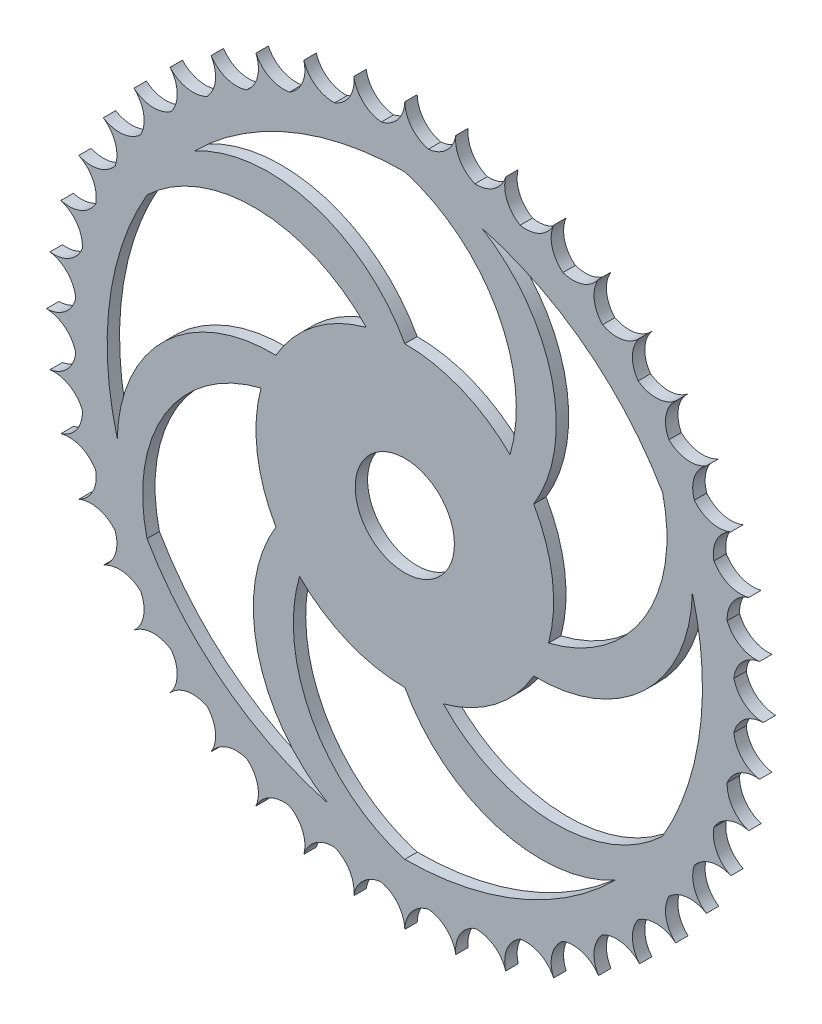
SolidWorks part; units mm, degrees
ref_plane "Alzado" through (0, 0, 0) normal (0, 0, 1) x (1, 0, 0)
ref_plane "Planta" through (0, 0, 0) normal (0, 1, 0) x (1, 0, 0)
ref_plane "Vista lateral" through (0, 0, 0) normal (1, 0, 0) x (0, 0, -1)
sketch "Croquis2" plane through (0, 0, 0) normal (0, 0, 1) x (1, 0, 0)
  line L0 (0, 0) -> (0, 131.9446) construction
  line L1 (0, 0) -> (9.1932, 128.5376) construction
  line L2 (0, 0) -> (-8.8645, 123.9425) construction
  line L3 (-6.025, 84.2398) -> (-6.0245, 84.2341)
  circle A0 centre (0, 0) radius 92.075
  arc A3 (0, 92.075) -> (6.025, 84.2398) centre (7.8948, 91.9118) ccw
  arc A4 (0, 92.075) -> (-6.025, 84.2398) centre (-7.8948, 91.9118) cw
  arc A5 (13.1036, 91.1378) -> (6.025, 84.2398) centre (5.2659, 92.0998) cw
  arc A6 (13.1036, 91.1378) -> (17.9522, 82.5249) centre (20.8949, 89.8527) ccw
  arc A7 (25.9405, 88.3453) -> (17.9522, 82.5249) centre (18.3195, 90.4129) cw
  arc A8 (25.9405, 88.3453) -> (29.514, 79.1301) centre (33.4696, 85.9645) ccw
  arc A9 (38.2493, 83.7544) -> (29.514, 79.1301) centre (31.0001, 86.8855) cw
  arc A10 (38.2493, 83.7544) -> (40.475, 74.1244) centre (45.3629, 80.3262) ccw
  arc A11 (49.7795, 77.4584) -> (40.475, 74.1244) centre (43.0497, 81.5894) cw
  arc A12 (49.7795, 77.4584) -> (50.612, 67.6097) centre (56.3328, 73.0528) ccw
  arc A13 (60.2963, 69.5856) -> (50.612, 67.6097) centre (54.2229, 74.6323) cw
  arc A14 (60.2963, 69.5856) -> (59.7187, 59.7187) centre (66.1559, 64.2923) ccw
  arc A15 (69.5856, 60.2963) -> (59.7187, 59.7187) centre (64.2923, 66.1559) cw
  arc A16 (69.5856, 60.2963) -> (67.6097, 50.612) centre (74.6323, 54.2229) ccw
  arc A17 (77.4584, 49.7795) -> (67.6097, 50.612) centre (73.0528, 56.3328) cw
  arc A18 (77.4584, 49.7795) -> (74.1244, 40.475) centre (81.5894, 43.0497) ccw
  arc A19 (83.7544, 38.2493) -> (74.1244, 40.475) centre (80.3262, 45.3629) cw
  arc A20 (83.7544, 38.2493) -> (79.1301, 29.514) centre (86.8855, 31.0001) ccw
  arc A21 (88.3453, 25.9405) -> (79.1301, 29.514) centre (85.9644, 33.4696) cw
  arc A22 (88.3453, 25.9405) -> (82.5249, 17.9522) centre (90.4129, 18.3195) ccw
  arc A23 (91.1378, 13.1036) -> (82.5249, 17.9522) centre (89.8527, 20.8949) cw
  arc A24 (91.1378, 13.1036) -> (84.2398, 6.025) centre (92.0998, 5.2659) ccw
  arc A25 (92.075, 0) -> (84.2398, 6.025) centre (91.9118, 7.8948) cw
  arc A26 (92.075, 0) -> (84.2398, -6.0249) centre (91.9118, -7.8948) ccw
  arc A27 (91.1378, -13.1036) -> (84.2398, -6.0249) centre (92.0998, -5.2659) cw
  arc A28 (91.1378, -13.1036) -> (82.5249, -17.9522) centre (89.8527, -20.8949) ccw
  arc A29 (88.3453, -25.9405) -> (82.5249, -17.9522) centre (90.4129, -18.3195) cw
  arc A30 (88.3453, -25.9405) -> (79.1301, -29.514) centre (85.9644, -33.4696) ccw
  arc A31 (83.7544, -38.2493) -> (79.1301, -29.514) centre (86.8855, -31.0001) cw
  arc A32 (83.7544, -38.2493) -> (74.1244, -40.475) centre (80.3262, -45.3629) ccw
  arc A33 (77.4584, -49.7795) -> (74.1244, -40.475) centre (81.5894, -43.0497) cw
  arc A34 (77.4584, -49.7795) -> (67.6097, -50.612) centre (73.0528, -56.3328) ccw
  arc A35 (69.5856, -60.2963) -> (67.6097, -50.612) centre (74.6323, -54.2229) cw
  arc A36 (69.5856, -60.2963) -> (59.7187, -59.7187) centre (64.2923, -66.1559) ccw
  arc A37 (60.2963, -69.5856) -> (59.7187, -59.7187) centre (66.1559, -64.2922) cw
  arc A38 (60.2963, -69.5856) -> (50.612, -67.6097) centre (54.2229, -74.6323) ccw
  arc A39 (49.7795, -77.4584) -> (50.612, -67.6097) centre (56.3328, -73.0528) cw
  arc A40 (49.7795, -77.4584) -> (40.475, -74.1244) centre (43.0497, -81.5894) ccw
  arc A41 (38.2493, -83.7544) -> (40.475, -74.1244) centre (45.3629, -80.3262) cw
  arc A42 (38.2493, -83.7544) -> (29.514, -79.1301) centre (31.0001, -86.8855) ccw
  arc A43 (25.9405, -88.3453) -> (29.514, -79.1301) centre (33.4696, -85.9644) cw
  arc A44 (25.9405, -88.3453) -> (17.9522, -82.5249) centre (18.3195, -90.4129) ccw
  arc A45 (13.1036, -91.1378) -> (17.9522, -82.5249) centre (20.8949, -89.8527) cw
  arc A46 (13.1036, -91.1378) -> (6.025, -84.2398) centre (5.2659, -92.0998) ccw
  arc A47 (0, -92.075) -> (6.025, -84.2398) centre (7.8948, -91.9117) cw
  arc A48 (0, -92.075) -> (-6.025, -84.2398) centre (-7.8948, -91.9117) ccw
  arc A49 (-13.1036, -91.1378) -> (-6.025, -84.2398) centre (-5.2659, -92.0998) cw
  arc A50 (-13.1036, -91.1378) -> (-17.9522, -82.5249) centre (-20.8949, -89.8527) ccw
  arc A51 (-25.9405, -88.3453) -> (-17.9522, -82.5249) centre (-18.3195, -90.4129) cw
  arc A52 (-25.9405, -88.3453) -> (-29.514, -79.1301) centre (-33.4696, -85.9644) ccw
  arc A53 (-38.2493, -83.7544) -> (-29.514, -79.1301) centre (-31.0001, -86.8855) cw
  arc A54 (-38.2493, -83.7544) -> (-40.475, -74.1244) centre (-45.3629, -80.3262) ccw
  arc A55 (-49.7795, -77.4584) -> (-40.475, -74.1244) centre (-43.0497, -81.5894) cw
  arc A56 (-49.7795, -77.4584) -> (-50.612, -67.6097) centre (-56.3328, -73.0528) ccw
  arc A57 (-60.2963, -69.5856) -> (-50.612, -67.6097) centre (-54.2229, -74.6323) cw
  arc A58 (-60.2963, -69.5856) -> (-59.7187, -59.7187) centre (-66.1559, -64.2922) ccw
  arc A59 (-69.5856, -60.2963) -> (-59.7187, -59.7187) centre (-64.2923, -66.1559) cw
  arc A60 (-69.5856, -60.2963) -> (-67.6097, -50.612) centre (-74.6323, -54.2229) ccw
  arc A61 (-77.4584, -49.7795) -> (-67.6097, -50.612) centre (-73.0528, -56.3328) cw
  arc A62 (-77.4584, -49.7795) -> (-74.1244, -40.475) centre (-81.5894, -43.0497) ccw
  arc A63 (-83.7544, -38.2493) -> (-74.1244, -40.475) centre (-80.3262, -45.3629) cw
  arc A64 (-83.7544, -38.2493) -> (-79.1301, -29.514) centre (-86.8855, -31.0001) ccw
  arc A65 (-88.3453, -25.9405) -> (-79.1301, -29.514) centre (-85.9644, -33.4696) cw
  arc A66 (-88.3453, -25.9405) -> (-82.5249, -17.9522) centre (-90.4129, -18.3195) ccw
  arc A67 (-91.1378, -13.1036) -> (-82.5249, -17.9522) centre (-89.8527, -20.8949) cw
  arc A68 (-91.1378, -13.1036) -> (-84.2398, -6.0249) centre (-92.0998, -5.2659) ccw
  arc A69 (-92.075, 0) -> (-84.2398, -6.0249) centre (-91.9118, -7.8948) cw
  arc A70 (-92.075, 0) -> (-84.2398, 6.025) centre (-91.9118, 7.8948) ccw
  arc A71 (-91.1378, 13.1036) -> (-84.2398, 6.025) centre (-92.0998, 5.2659) cw
  arc A72 (-91.1378, 13.1036) -> (-82.5249, 17.9522) centre (-89.8527, 20.8949) ccw
  arc A73 (-88.3453, 25.9405) -> (-82.5249, 17.9522) centre (-90.4129, 18.3195) cw
  arc A74 (-88.3453, 25.9405) -> (-79.1301, 29.514) centre (-85.9644, 33.4696) ccw
  arc A75 (-83.7544, 38.2493) -> (-79.1301, 29.514) centre (-86.8855, 31.0001) cw
  arc A76 (-83.7544, 38.2493) -> (-74.1244, 40.475) centre (-80.3262, 45.3629) ccw
  arc A77 (-77.4584, 49.7795) -> (-74.1244, 40.475) centre (-81.5894, 43.0497) cw
  arc A78 (-77.4584, 49.7795) -> (-67.6097, 50.612) centre (-73.0528, 56.3328) ccw
  arc A79 (-69.5856, 60.2963) -> (-67.6097, 50.612) centre (-74.6323, 54.2229) cw
  arc A80 (-69.5856, 60.2963) -> (-59.7187, 59.7187) centre (-64.2923, 66.1559) ccw
  arc A81 (-60.2963, 69.5856) -> (-59.7187, 59.7187) centre (-66.1559, 64.2923) cw
  arc A82 (-60.2963, 69.5856) -> (-50.612, 67.6097) centre (-54.2229, 74.6323) ccw
  arc A83 (-49.7795, 77.4584) -> (-50.612, 67.6097) centre (-56.3328, 73.0528) cw
  arc A84 (-49.7795, 77.4584) -> (-40.475, 74.1244) centre (-43.0497, 81.5894) ccw
  arc A85 (-38.2493, 83.7544) -> (-40.475, 74.1244) centre (-45.3629, 80.3262) cw
  arc A86 (-38.2493, 83.7544) -> (-29.514, 79.1301) centre (-31.0001, 86.8855) ccw
  arc A87 (-25.9405, 88.3453) -> (-29.514, 79.1301) centre (-33.4696, 85.9645) cw
  arc A88 (-25.9405, 88.3453) -> (-17.9522, 82.5249) centre (-18.3195, 90.4129) ccw
  arc A89 (-13.1036, 91.1378) -> (-17.9522, 82.5249) centre (-20.8949, 89.8527) cw
  arc A90 (-13.1036, 91.1378) -> (-6.025, 84.2398) centre (-5.2659, 92.0998) ccw
  point P111 (0, 0)
  point P232 (0, 0)
  dimension "D1" = 184.15
  dimension "D5" = 44
  dimension "D3" = 4.091
  dimension "D4" = 4.091
extrude "Saliente-Extruir1" add sketch "Croquis2" along normal mid plane 3.175 contours A90 A89 A88 A87 A86 A85 A84 A83 A82 A81 A80 A79 A78 A77 A76 A75 A74 A73 A72 A71 A70 A69 A68 A67 A66 A65 A64 A63 A62 A61 A60 A59 A58 A57 A56 A55 A54 A53 A52 A51 A50 A49 A48 A47 A46 A45 A44 A43 A42 A41 A40 region at (0, 0, 0)
sketch "Croquis3" plane through (0, 0, 1.5875) normal (0, 0, 1) x (1, 0, 0)
  line L1 (0, 38.1) -> (0, 91.7485) construction
  arc A0 (0, 76.2) -> (-53.8815, 53.8815) centre (0, 0) ccw
  arc A1 (26.9408, 26.9408) -> (0, 38.1) centre (0, 0) ccw
  arc A2 (-53.8815, 53.8815) -> (0, 38.1) centre (-34.8315, 19.05) cw
  arc A3 (26.9408, 26.9408) -> (0, 76.2) centre (-11.1592, 38.1) ccw
  arc A4 (65.9911, 38.1) -> (19.722, 73.6035) centre (0, 0) ccw
  arc A5 (19.722, 73.6035) -> (32.9956, 19.05) centre (-0.918, 39.69) cw
  arc A6 (36.8018, -9.861) -> (32.9956, 19.05) centre (0, 0) ccw
  arc A7 (36.8018, -9.861) -> (65.9911, 38.1) centre (27.416, 28.7142) ccw
  arc A8 (65.9911, -38.1) -> (73.6035, 19.722) centre (0, 0) ccw
  arc A9 (73.6035, 19.722) -> (32.9956, -19.05) centre (33.9136, 20.64) cw
  arc A10 (9.861, -36.8018) -> (32.9956, -19.05) centre (0, 0) ccw
  arc A11 (9.861, -36.8018) -> (65.9911, -38.1) centre (38.5752, -9.3858) ccw
  arc A12 (0, -76.2) -> (53.8815, -53.8815) centre (0, 0) ccw
  arc A13 (53.8815, -53.8815) -> (0, -38.1) centre (34.8315, -19.05) cw
  arc A14 (-26.9408, -26.9408) -> (0, -38.1) centre (0, 0) ccw
  arc A15 (-26.9408, -26.9408) -> (0, -76.2) centre (11.1592, -38.1) ccw
  arc A16 (-65.9911, -38.1) -> (-19.722, -73.6035) centre (0, 0) ccw
  arc A17 (-19.722, -73.6035) -> (-32.9956, -19.05) centre (0.918, -39.69) cw
  arc A18 (-36.8018, 9.861) -> (-32.9956, -19.05) centre (0, 0) ccw
  arc A19 (-36.8018, 9.861) -> (-65.9911, -38.1) centre (-27.416, -28.7142) ccw
  arc A20 (-65.9911, 38.1) -> (-73.6035, -19.722) centre (0, 0) ccw
  arc A21 (-73.6035, -19.722) -> (-32.9956, 19.05) centre (-33.9136, -20.64) cw
  arc A22 (-9.861, 36.8018) -> (-32.9956, 19.05) centre (0, 0) ccw
  arc A23 (-9.861, 36.8018) -> (-65.9911, 38.1) centre (-38.5752, 9.3858) ccw
  circle A24 centre (0, 0) radius 12.7
  point P43 (0, 0)
  dimension "D1" = 152.4
  dimension "D2" = 76.2
  dimension "D4" = 25.4
  dimension "D3" = 6
extrude "Cortar-Extruir1" cut sketch "Croquis3" against normal through all
ref_axis "Eje1" through (-101.2825, 0, 0) along (1, 0, 0)
sketch "Croquis7" plane through (0, 0, 0) normal (0, 0, 1) x (1, 0, 0)
  circle A0 centre (0, 0) radius 85.344
  dimension "D1" = 170.688
